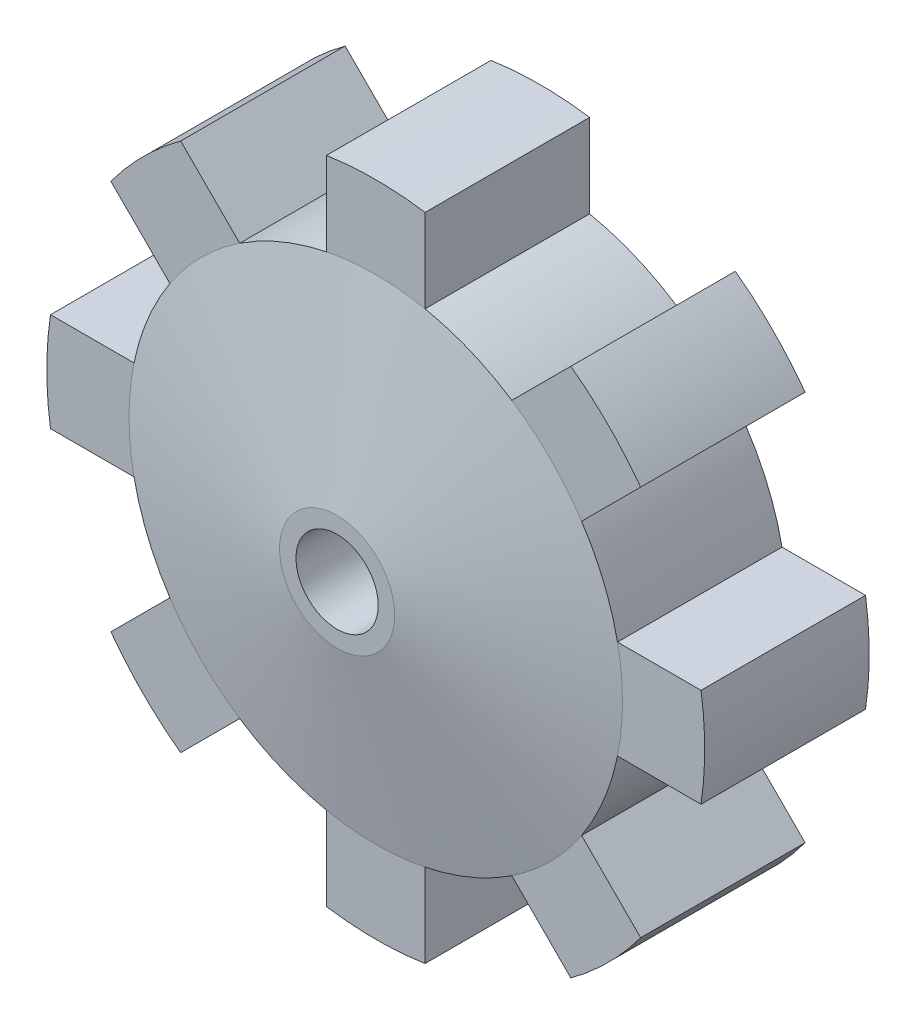
SolidWorks part; units mm, degrees
ref_plane "Front Plane" through (0, 0, 0) normal (0, 0, 1) x (1, 0, 0)
ref_plane "Top Plane" through (0, 0, 0) normal (0, 1, 0) x (1, 0, 0)
ref_plane "Right Plane" through (0, 0, 0) normal (1, 0, 0) x (0, 0, -1)
sketch "Sketch3" plane through (0, 0, 0) normal (1, 0, 0) x (0, 0, -1)
  line L0 (0, 0) -> (14.7, 0)
  line L4 (2.35, 15) -> (2.35, 20)
  line L5 (2.35, 20) -> (12.35, 20)
  line L6 (12.35, 20) -> (12.35, 15)
  line L8 (0, 3.5) -> (0, 0)
  line L9 (14.7, 3.5) -> (14.7, 0)
  line L10 (2.35, 15) -> (0, 3.5)
  line L11 (12.35, 15) -> (14.7, 3.5)
  dimension "D1" = 14.7
  dimension "D2" = 5
  dimension "D3" = 10
  dimension "D4" = 20
  dimension "D5" = 3.5
revolve "Revolve3" add sketch "Sketch3" angle 360 about L0
sketch "Sketch2" plane through (0, 0, 0) normal (0, 0, 1) x (1, 0, 0)
  line L1 (3, 14.6969) -> (3, 19.7737)
  line L2 (3, 19.7737) -> (-3, 19.7737)
  line L3 (-3, 19.7737) -> (-3, 14.6969)
  line L4 (11.8608, 16.1035) -> (8.271, 12.5136)
  line L5 (16.1035, 11.8608) -> (11.8608, 16.1035)
  line L6 (12.5136, 8.271) -> (16.1035, 11.8608)
  line L7 (19.7737, 3) -> (14.6969, 3)
  line L8 (19.7737, -3) -> (19.7737, 3)
  line L9 (14.6969, -3) -> (19.7737, -3)
  line L10 (16.1035, -11.8608) -> (12.5136, -8.271)
  line L11 (11.8608, -16.1035) -> (16.1035, -11.8608)
  line L12 (8.271, -12.5136) -> (11.8608, -16.1035)
  line L13 (3, -19.7737) -> (3, -14.6969)
  line L14 (-3, -19.7737) -> (3, -19.7737)
  line L15 (-3, -14.6969) -> (-3, -19.7737)
  line L16 (-11.8608, -16.1035) -> (-8.271, -12.5136)
  line L17 (-16.1035, -11.8608) -> (-11.8608, -16.1035)
  line L18 (-12.5136, -8.271) -> (-16.1035, -11.8608)
  line L19 (-19.7737, -3) -> (-14.6969, -3)
  line L20 (-19.7737, 3) -> (-19.7737, -3)
  line L21 (-14.6969, 3) -> (-19.7737, 3)
  line L22 (-16.1035, 11.8608) -> (-12.5136, 8.271)
  line L23 (-11.8608, 16.1035) -> (-16.1035, 11.8608)
  line L24 (-8.271, 12.5136) -> (-11.8608, 16.1035)
  circle A0 centre (0, 0) radius 20
  circle A1 centre (0, 0) radius 15
  circle A2 centre (0, 0) radius 25
  circle A3 centre (0, 0) radius 2.5
  point P39 (0, 0)
  dimension "D1" = 40
  dimension "D2" = 30
  dimension "D5" = 50
  dimension "D6" = 5
  dimension "D3" = 6
  dimension "D4" = 8
extrude "Cut-Extrude5" cut sketch "Sketch2" against normal blind 30 contours A3 | A2 A0 | A1 L19 A0 L18 | A1 L22 A0 L21 | A1 L3 A0 L24 | A1 L4 A0 L1 | A1 L7 A0 L6 | A1 L10 A0 L9 | A1 L13 A0 L12 | A1 L16 A0 L15 region at (6.7225, 16.2295, 0) region at (-6.7225, 16.2295, 0) region at (16.2295, 6.7225, 0) region at (-16.2295, 6.7225, 0) region at (16.2295, -6.7225, 0) region at (-16.2295, -6.7225, 0) region at (6.7225, -16.2295, 0) region at (-6.7225, -16.2295, 0) region at (-24.2929, 0, 0) region at (0, 0, 0)
